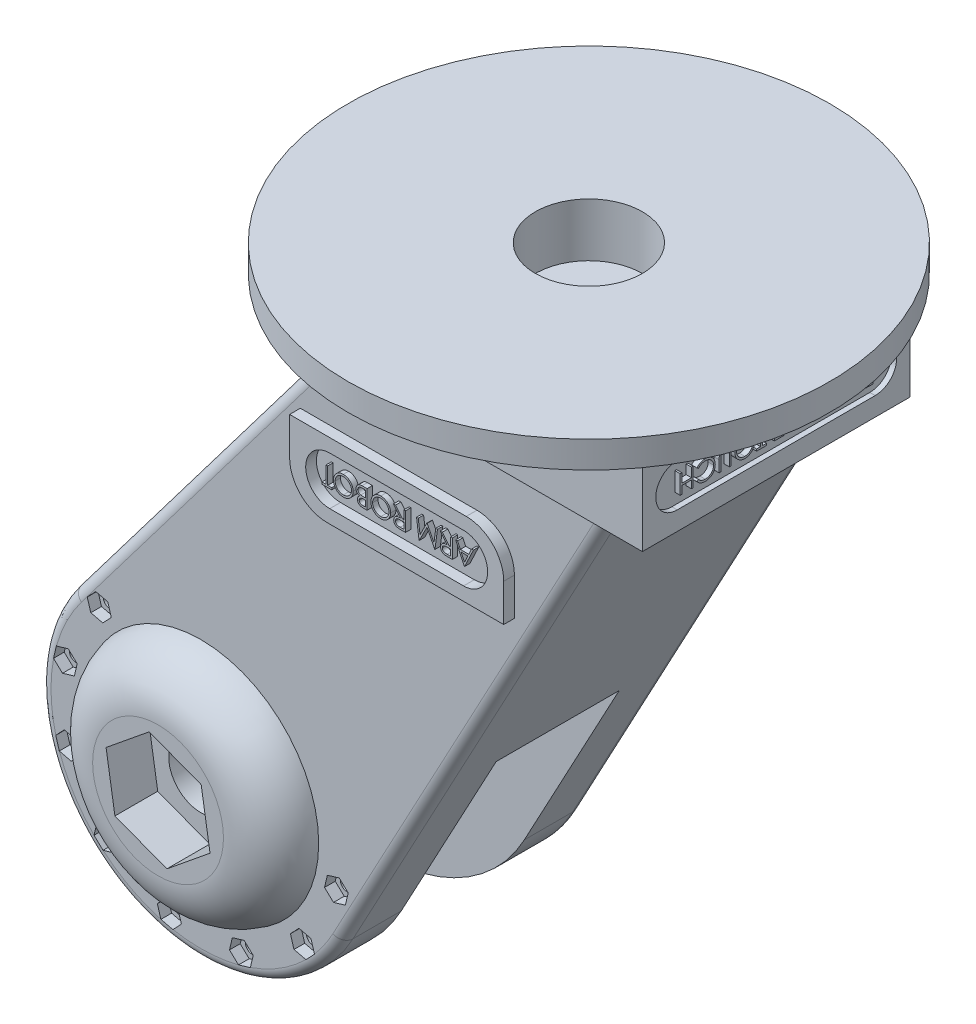
SolidWorks part; units mm, degrees
ref_plane "Front Plane" through (0, 0, 0) normal (0, 0, 1) x (1, 0, 0)
ref_plane "Top Plane" through (0, 0, 0) normal (0, 1, 0) x (1, 0, 0)
ref_plane "Right Plane" through (0, 0, 0) normal (1, 0, 0) x (0, 0, -1)
sketch "Sketch1" plane through (0, 0, 0) normal (0, 1, 0) x (1, 0, 0)
  circle A0 centre (0, 0) radius 45
  dimension "D1" = 90
extrude "Boss-Extrude1" add sketch "Sketch1" along normal blind 5
sketch "Sketch2" plane through (0, 5, 0) normal (0, 1, 0) x (1, 0, 0)
  line L1 (35, -25) -> (-35, -25)
  line L2 (35, -25) -> (35, 25)
  line L3 (35, 25) -> (-35, 25)
  line L4 (-35, -25) -> (-35, 25)
  line L5 (35, -25) -> (-35, 25) construction
  line L6 (35, 25) -> (-35, -25) construction
  point P0 (0, 0)
  dimension "D1" = 50
  dimension "D2" = 70
extrude "Boss-Extrude2" add sketch "Sketch2" along normal blind 15
sketch "Sketch3" plane through (0, 0, 0) normal (0, 0, 1) x (1, 0, 0)
  line L0 (-45, 0) -> (45, 0) construction
  line L2 (-27, 20) -> (-73.907, 81.8767)
  line L3 (-35, 20) -> (35, 20) construction
  line L4 (27, 20) -> (-23.5684, 114.1904)
  line L5 (-27, 20) -> (27, 20)
  arc A0 (-23.5684, 114.1904) -> (-73.907, 81.8767) centre (-50, 100) ccw
  dimension "D1" = 60
  dimension "D2" = 100
  dimension "D3" = 50
  dimension "D4" = 8
  dimension "D5" = 8
extrude "Boss-Extrude3" add sketch "Sketch3" along normal mid plane 45
sketch "Sketch4" plane through (0, 0, 22.5) normal (0, 0, 1) x (1, 0, 0)
  circle A0 centre (-50, 100) radius 22.0198
extrude "Boss-Extrude4" add sketch "Sketch4" along normal blind 8
fillet "Fillet1" radius 10 1 edges at (-27.9802, 100, 30.5)
sketch "Sketch5" plane through (0, 0, 30.5) normal (0, 0, 1) x (1, 0, 0)
  line L1 (-58.0596, 106.5607) -> (-59.7115, 96.3005)
  line L2 (-59.7115, 96.3005) -> (-51.6519, 89.7398)
  line L3 (-51.6519, 89.7398) -> (-41.9404, 93.4393)
  line L4 (-41.9404, 93.4393) -> (-40.2885, 103.6995)
  line L5 (-40.2885, 103.6995) -> (-48.3481, 110.2602)
  line L6 (-48.3481, 110.2602) -> (-58.0596, 106.5607)
  circle A0 centre (-50, 100) radius 9 construction
  dimension "D1" = 18
extrude "Cut-Extrude1" cut sketch "Sketch5" against normal blind 8
sketch "Sketch7" plane through (29.294, 15.7272, 0) normal (0.8811, 0.473, 0) x (0, 0, -1)
  line L0 (-22.5, 111.7562) -> (22.5, 111.7562) construction
  line L1 (11.5, 74.2562) -> (-11.5, 74.2562)
  line L2 (11.5, 74.2562) -> (11.5, 149.2562)
  line L3 (11.5, 149.2562) -> (-11.5, 149.2562)
  line L4 (-11.5, 74.2562) -> (-11.5, 149.2562)
  line L5 (11.5, 74.2562) -> (-11.5, 149.2562) construction
  line L6 (11.5, 149.2562) -> (-11.5, 74.2562) construction
  point P0 (0, 111.7562)
  dimension "D1" = 23
  dimension "D2" = 75
extrude "Cut-Extrude2" cut sketch "Sketch7" against normal blind 72
sketch "Sketch8" plane through (0, 0, 22.5) normal (0, 0, 1) x (1, 0, 0)
  circle A0 centre (-50, 100) radius 6
  dimension "D1" = 12
extrude "Cut-Extrude3" cut sketch "Sketch8" against normal blind 20
sketch "Sketch9" plane through (0, 0, 22.5) normal (0, 0, 1) x (1, 0, 0)
  line L0 (-50, 122.0198) -> (-50, 130) construction
  line L2 (-32.6021, 119.4326) -> (-33.2634, 117.2199)
  line L3 (-33.2634, 117.2199) -> (-31.6777, 115.5409)
  line L4 (-31.6777, 115.5409) -> (-29.4309, 116.0745)
  line L5 (-29.4309, 116.0745) -> (-28.7696, 118.2872)
  line L6 (-28.7696, 118.2872) -> (-30.3552, 119.9663)
  line L7 (-30.3552, 119.9663) -> (-32.6021, 119.4326)
  circle A0 centre (-50, 100) radius 22.0198 construction
  arc A1 (-23.5684, 114.1904) -> (-73.907, 81.8767) centre (-50, 100) ccw construction
  circle A2 centre (-31.0165, 117.7536) radius 2 construction
  point P9 (-29.1002, 117.1809)
  point P17 (-33.6804, 114.7831)
  dimension "D1" = 4
  dimension "D2" = 3.99
extrude "Cut-Extrude4" cut sketch "Sketch9" against normal blind 2
sketch "Sketch10" plane through (0, 0, 20.5) normal (0, 0, 1) x (1, 0, 0)
  circle A0 centre (-31.0165, 117.7536) radius 1.25
  dimension "D1" = 2.5
extrude "Cut-Extrude5" cut sketch "Sketch10" against normal blind 1
pattern_circular "CirPattern1" count 12 over 360 about axis through (-50, 100, 22.5) along (0, 0, 1) skipping 7, 8, 9, 10 of "Cut-Extrude5", "Cut-Extrude4"
sketch "Sketch11" plane through (0, 0, 22.5) normal (0, 0, 1) x (1, 0, 0)
  line L0 (-50, 100) -> (0, 20) construction
  line L1 (-27, 20) -> (27, 20) construction
  line L3 (8.5858, 31.2627) -> (-31.4142, 31.2627)
  line L4 (8.5858, 31.2627) -> (8.5858, 45.2627)
  line L5 (8.5858, 45.2627) -> (-31.4142, 45.2627)
  line L6 (-31.4142, 31.2627) -> (-31.4142, 45.2627)
  line L7 (8.5858, 31.2627) -> (-31.4142, 45.2627) construction
  line L8 (8.5858, 45.2627) -> (-31.4142, 31.2627) construction
  point P5 (-11.4142, 38.2627)
  dimension "D1" = 14
  dimension "D2" = 40
extrude "Boss-Extrude5" add sketch "Sketch11" along normal blind 2
sketch "Sketch12" plane through (0, 0, 24.5) normal (0, 0, 1) x (1, 0, 0)
  line L0 (-23.9142, 38.2627) -> (1.0858, 38.2627) construction
  line L1 (-23.9142, 42.7627) -> (1.0858, 42.7627)
  line L2 (-23.9142, 33.7627) -> (1.0858, 33.7627)
  line L3 (-31.4142, 45.2627) -> (-31.4142, 31.2627) construction
  line L4 (8.5858, 31.2627) -> (8.5858, 45.2627) construction
  line L5 (8.5858, 45.2627) -> (-31.4142, 45.2627) construction
  line L6 (-31.4142, 31.2627) -> (8.5858, 31.2627) construction
  arc A0 (-23.9142, 42.7627) -> (-23.9142, 33.7627) centre (-23.9142, 38.2627) ccw
  arc A1 (1.0858, 33.7627) -> (1.0858, 42.7627) centre (1.0858, 38.2627) ccw
  point P2 (-11.4142, 38.2627)
  dimension "D1" = 7.5
  dimension "D2" = 7.5
  dimension "D3" = 2.5
  dimension "D4" = 2.5
extrude "Cut-Extrude6" cut sketch "Sketch12" against normal blind 2
fillet "Fillet3" radius 7 2 edges at (8.5858, 31.2627, 23.5) (-31.4142, 45.2627, 23.5)
ref_plane "Plane1" through (0, 0, 0) normal (0, 0, -1) x (-1, 0, 0)
mirror "Mirror1" about plane through (0, 0, 0) normal (0, 0, -1) of "Fillet3", "Cut-Extrude6", "Boss-Extrude5", "CirPattern1", "Cut-Extrude5", "Cut-Extrude4", "Cut-Extrude3", "Cut-Extrude2", "Cut-Extrude1", "Fillet1", "Boss-Extrude4"
sketch "Sketch15" plane through (0, 0, -22.5) normal (0, 0, -1) x (-1, 0, 0)
  text T0 "ARM ROBOT"
extrude "Boss-Extrude6" add sketch "Sketch15" along normal blind 1
sketch "Sketch16" plane through (0, 0, 22.5) normal (0, 0, 1) x (1, 0, 0)
  line L0 (1.0858, 42.7627) -> (-23.9142, 42.7627) construction
  line L1 (-23.9142, 33.7627) -> (1.0858, 33.7627) construction
  text T0 "ARM_LSB"
  point P1 (-21.936, 33.7627)
  point P4 (-21.936, 42.7627)
  dimension "D1" = 6.5
  dimension "D2" = 9
extrude "Boss-Extrude7" add sketch "Sketch16" along normal blind 1
sketch "Sketch17" plane through (35, 0, 0) normal (1, 0, 0) x (0, 0, -1)
  line L0 (-18.5, 12.5) -> (18.5, 12.5) construction
  line L1 (-18.5, 16.5) -> (18.5, 16.5)
  line L2 (-18.5, 8.5) -> (18.5, 8.5)
  line L3 (-25, 20) -> (-25, 5) construction
  line L4 (25, 20) -> (25, 5) construction
  line L5 (-25, 20) -> (25, 20) construction
  line L6 (-25, 5) -> (25, 5) construction
  arc A0 (-18.5, 16.5) -> (-18.5, 8.5) centre (-18.5, 12.5) ccw
  arc A1 (18.5, 8.5) -> (18.5, 16.5) centre (18.5, 12.5) ccw
  point P2 (0, 12.5)
  dimension "D1" = 6.5
  dimension "D2" = 6.5
  dimension "D3" = 3.5
  dimension "D4" = 3.5
extrude "Cut-Extrude7" cut sketch "Sketch17" against normal blind 1
sketch "Sketch18" plane through (34, 0, 0) normal (1, 0, 0) x (0, 0, -1)
  text T0 "DO NOT TOUCH"
extrude "Boss-Extrude8" add sketch "Sketch18" along normal blind 1
sketch "Sketch19" plane through (0, 0, 0) normal (0, -1, 0) x (1, 0, 0)
  circle A0 centre (0, 0) radius 10
  dimension "D1" = 20
extrude "Cut-Extrude8" cut sketch "Sketch19" against normal blind 10 contours A0
fillet "Fillet4" radius 2 3 edges at (-50.4535, 50.9384, 22.5) (-66.2061, 125.246, 22.5) (1.7158, 67.0952, 22.5)
fillet "Fillet5" radius 2 3 edges at (-50.4535, 50.9384, -22.5) (-66.2061, 125.246, -22.5) (1.7158, 67.0952, -22.5)
sketch "Sketch20" plane through (0, 0, 0) normal (0, 0, 1) x (1, 0, 0)
  point P0 (-50, 100)
sketch "Sketch21" plane through (0, 0, 0) normal (0, 0, 1) x (1, 0, 0)
  point P0 (-50, 100)
move or copy body "Body-Move/Copy1" bodies to move or copy 118 copy no translate (50, -100, 0)
move or copy body "Body-Move/Copy2" bodies to move or copy 124 copy no rotation origin (0, 0, 0) rotation axis (1, 0, 0) rotation angle 180
